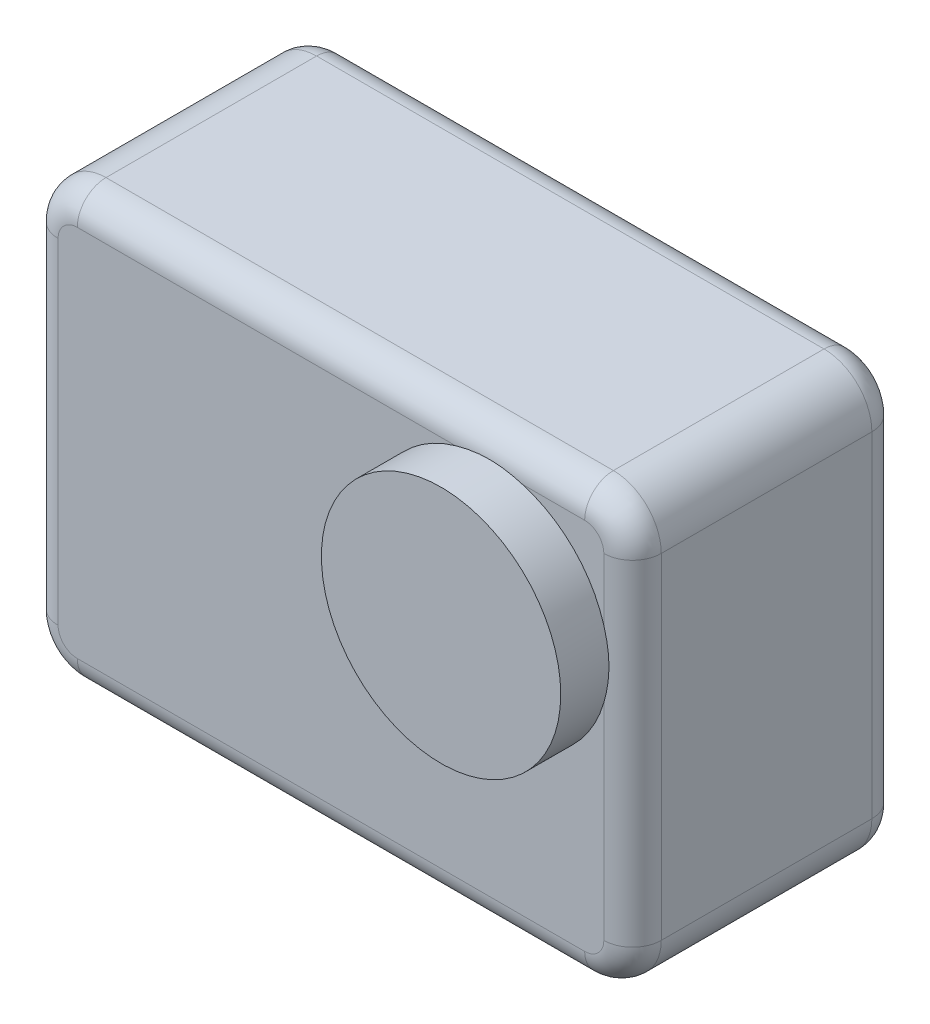
SolidWorks part; units mm, degrees
ref_plane "Front Plane" through (0, 0, 0) normal (0, 0, 1) x (1, 0, 0)
ref_plane "Top Plane" through (0, 0, 0) normal (0, 1, 0) x (1, 0, 0)
ref_plane "Right Plane" through (0, 0, 0) normal (1, 0, 0) x (0, 0, -1)
sketch "Sketch3" plane through (0, 0, 0) normal (0, 0, 1) x (1, 0, 0)
  line L1 (5, 0) -> (58, 0)
  line L2 (0, 5) -> (0, 40)
  line L3 (5, 45) -> (58, 45)
  line L4 (63, 5) -> (63, 40)
  arc A0 (5, 0) -> (0, 5) centre (5, 5) cw
  arc A1 (58, 0) -> (63, 5) centre (58, 5) ccw
  arc A2 (58, 45) -> (63, 40) centre (58, 40) cw
  arc A3 (0, 40) -> (5, 45) centre (5, 40) cw
  point P7 (0, 0)
  point P10 (63, 0)
  point P15 (0, 45)
  dimension "D3" = 5
  dimension "D1" = 45
  dimension "D2" = 63
extrude "Boss-Extrude1" add sketch "Sketch3" along normal blind 28
fillet "Fillet1" radius 3 16 edges at (31.5, 0, 0) (61.5355, 1.4645, 0) (63, 22.5, 0) (61.5355, 43.5355, 0) (31.5, 45, 0) (1.4645, 43.5355, 0) (0, 22.5, 0) (1.4645, 1.4645, 0) (0, 22.5, 28) (1.4645, 43.5355, 28) (31.5, 45, 28) (61.5355, 43.5355, 28) (63, 22.5, 28) (61.5355, 1.4645, 28) (31.5, 0, 28) (1.4645, 1.4645, 28)
sketch "Sketch4" plane through (0, 0, 28) normal (0, 0, 1) x (1, 0, 0)
  line L0 (58, 42) -> (5, 42) construction
  line L1 (60, 5) -> (60, 40) construction
  circle A0 centre (48, 30) radius 12.5
  dimension "D1" = 25
  dimension "D2" = 12
  dimension "D3" = 12
extrude "Boss-Extrude3" add sketch "Sketch4" along normal mid plane 10 contours A0
